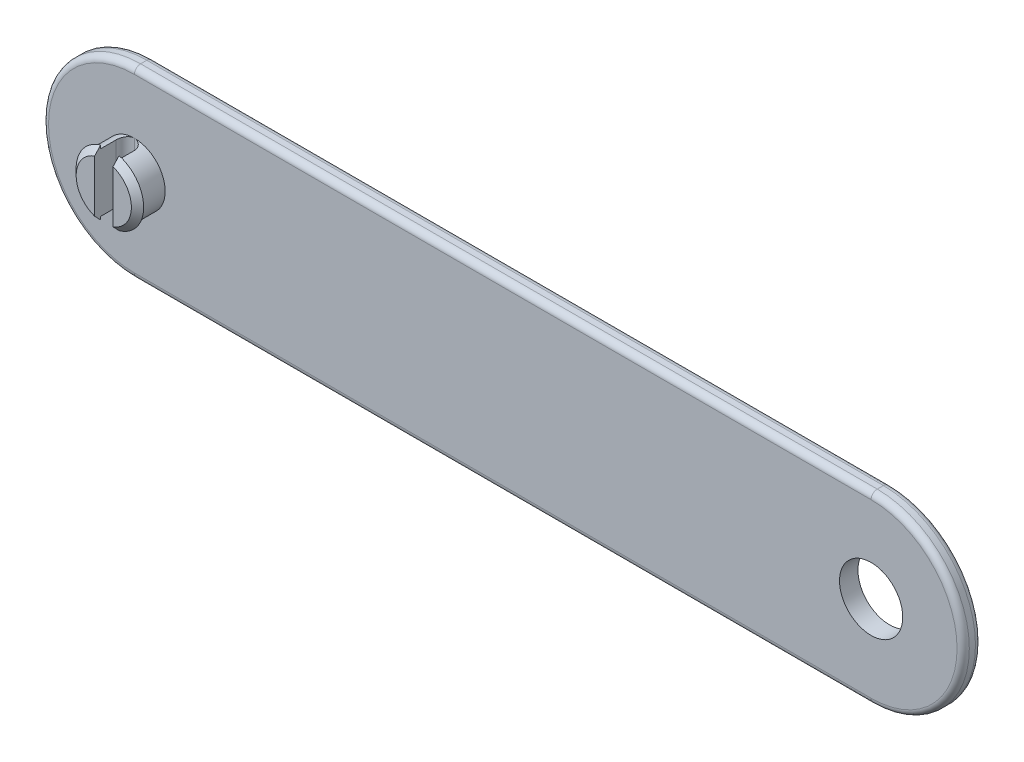
SolidWorks part; units mm, degrees
ref_plane "前视基准面" through (0, 0, 0) normal (0, 0, 1) x (1, 0, 0)
ref_plane "上视基准面" through (0, 0, 0) normal (0, 1, 0) x (1, 0, 0)
ref_plane "右视基准面" through (0, 0, 0) normal (1, 0, 0) x (0, 0, -1)
sketch "草图1" plane through (0, 0, 0) normal (0, 0, 1) x (1, 0, 0)
  line L0 (0, 0) -> (120, 0) construction
  line L1 (0, 15) -> (120, 15)
  line L2 (0, -15) -> (120, -15)
  arc A0 (0, 15) -> (0, -15) centre (0, 0) ccw
  arc A1 (120, -15) -> (120, 15) centre (120, 0) ccw
  circle A2 centre (120, 0) radius 5.15
  point P3 (60, 0)
  dimension "D2" = 15
  dimension "D3" = 10.3
  dimension "D1" = 120
extrude "凸台-拉伸1" add sketch "草图1" along normal blind 3 contours L1 A1 L2 A0
sketch "草图2" plane through (0, 0, 3) normal (0, 0, 1) x (1, 0, 0)
  line L2 (-1.5, 4.7697) -> (-1.5, -4.7697)
  line L4 (1.5, 4.7697) -> (1.5, -4.7697)
  arc A0 (-1.5, 4.7697) -> (-1.5, -4.7697) centre (0, 0) ccw
  arc A1 (1.5, -4.7697) -> (1.5, 4.7697) centre (0, 0) ccw
  dimension "D1" = 10
  dimension "D2" = 3
extrude "凸台-拉伸2" add sketch "草图2" along normal blind 4
sketch "草图5" plane through (0, 0, 7) normal (0, 0, 1) x (1, 0, 0)
  line L2 (-1.5, 5.2915) -> (-1.5, -5.2915)
  line L4 (1.5, 5.2915) -> (1.5, -5.2915)
  arc A0 (-1.5, 5.2915) -> (-1.5, -5.2915) centre (0, 0) ccw
  arc A1 (1.5, -5.2915) -> (1.5, 5.2915) centre (0, 0) ccw
  dimension "D1" = 11
  dimension "D2" = 3
extrude "凸台-拉伸3" add sketch "草图5" along normal blind 1
chamfer "倒角1" distance 1 angle 45 2 edges at (5.5, 0, 8) (-5.5, 0, 8)
extrude "切除-拉伸1" cut sketch "草图1<3>" along normal blind 5 contours A2 region at (120, 0, 0)
sketch "草图1<3>" plane through (0, 0, 0) normal (0, 0, 1) x (1, 0, 0) same geometry as "草图1"
fillet "圆角1" radius 1.5 2 edges at (-1.5, 0, 3) (1.5, 0, 3)
fillet "圆角2" radius 1 8 edges at (-15, 0, 0) (60, -15, 0) (135, 0, 0) (-15, 0, 3) (60, -15, 3) (135, 0, 3) (60, 15, 0) (60, 15, 3)
